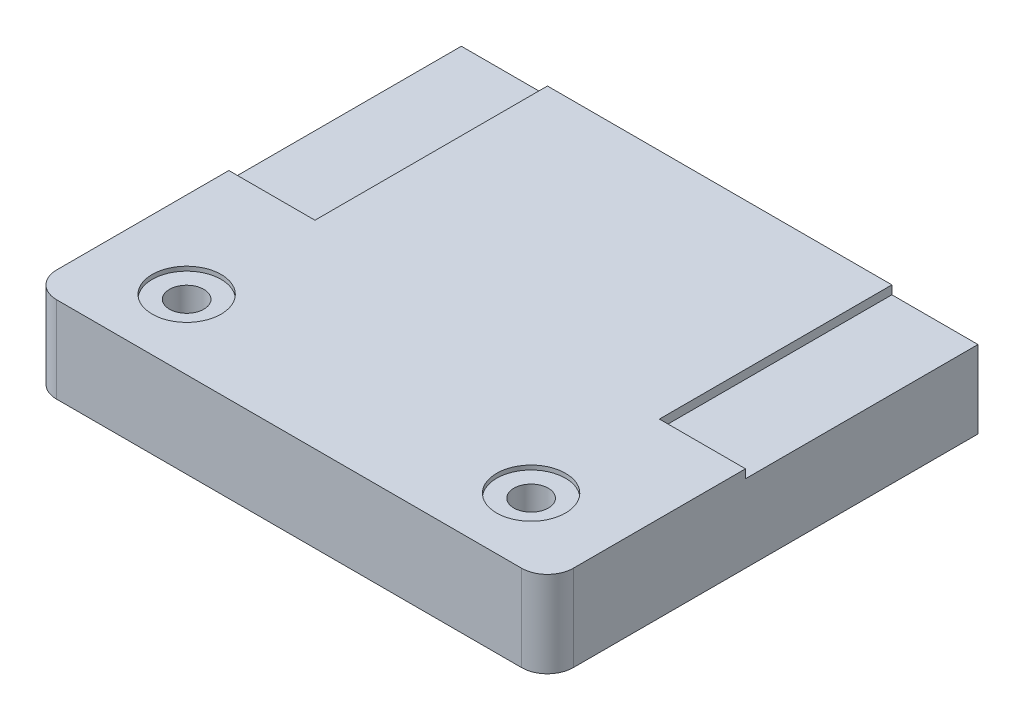
SolidWorks part; units mm, degrees
ref_plane "前视基准面" through (0, 0, 0) normal (0, 0, 1) x (1, 0, 0)
ref_plane "上视基准面" through (0, 0, 0) normal (0, 1, 0) x (1, 0, 0)
ref_plane "右视基准面" through (0, 0, 0) normal (1, 0, 0) x (0, 0, -1)
sketch "草图1" plane through (0, 0, 0) normal (0, 1, 0) x (1, 0, 0)
  line L1 (-30, 25) -> (30, 25)
  line L2 (-30, 25) -> (-30, -25)
  line L3 (-30, -25) -> (30, -25)
  line L4 (30, 25) -> (30, -25)
  line L5 (-30, 25) -> (30, -25) construction
  line L6 (-30, -25) -> (30, 25) construction
  point P0 (0, 0)
  dimension "D1" = 60
  dimension "D2" = 50
extrude "凸台-拉伸1" add sketch "草图1" along normal blind 10
fillet "圆角1" radius 3 2 edges at (-30, 5, 25) (30, 5, 25)
sketch "草图2" plane through (0, 10, 0) normal (0, 1, 0) x (1, 0, 0)
  line L0 (0, 0) -> (0, -25) construction
  line L1 (-27, -25) -> (27, -25) construction
  circle A0 centre (-20, -16.9) radius 4
  circle A1 centre (20, -16.9) radius 4
  dimension "D1" = 8
  dimension "D2" = 40
  dimension "D3" = 8.1
extrude "切除-拉伸1" cut sketch "草图2" against normal blind 0.5 contours A1 | A0
sketch "草图4" plane through (0, 10, 0) normal (0, 1, 0) x (1, 0, 0)
  line L1 (-20, -2) -> (-30, -2)
  line L2 (-20, -2) -> (-20, 25)
  line L3 (-20, 25) -> (-30, 25)
  line L4 (-30, -2) -> (-30, 25)
  line L5 (20, -2) -> (30, -2)
  line L6 (20, -2) -> (20, 25)
  line L7 (20, 25) -> (30, 25)
  line L8 (30, -2) -> (30, 25)
extrude "切除-拉伸2" cut sketch "草图4" against normal blind 1
sketch "草图5" plane through (0, 10, 0) normal (0, 1, 0) x (1, 0, 0)
  circle A0 centre (-20, -16.9) radius 2
  circle A1 centre (20, -16.9) radius 2
  dimension "D1" = 4
extrude "切除-拉伸3" cut sketch "草图5" against normal through all
